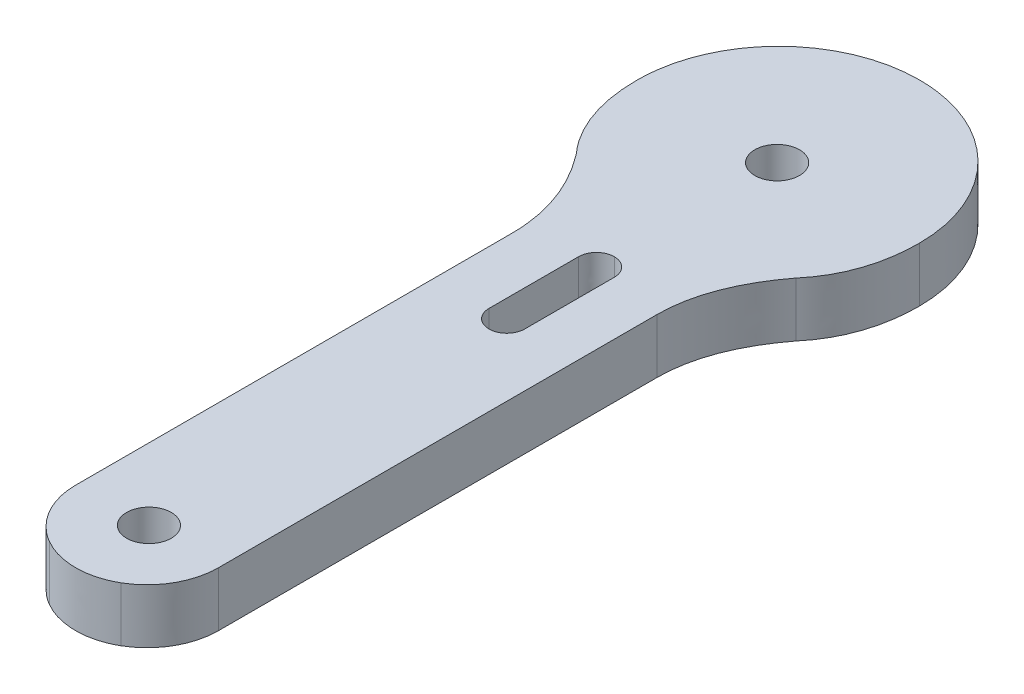
SolidWorks part; units mm, degrees
material "Acrylic (Medium-high impact)"
ref_plane "Front Plane" through (0, 0, 0) normal (0, 0, 1) x (1, 0, 0)
ref_plane "Top Plane" through (0, 0, 0) normal (0, 1, 0) x (1, 0, 0)
ref_plane "Right Plane" through (0, 0, 0) normal (1, 0, 0) x (0, 0, -1)
sketch "Sketch1" plane through (0, 0, 0) normal (0, 1, 0) x (1, 0, 0)
  line L0 (-9.7573, 16.2888) -> (-9.7571, 13.6387) construction
  line L1 (-5.7645, 4.2659) -> (-5.7642, -20.2368)
  line L2 (-13.75, -20.2368) -> (-13.75, 4.1172)
  line L3 (-10.7553, 4.8633) -> (-10.7553, -0.1369)
  line L4 (-8.7589, -0.1369) -> (-8.7589, 4.8633)
  line L5 (-11.0795, -20.1369) -> (-8.4347, -20.1369) construction
  circle A0 centre (-9.7571, -20.1369) radius 1.25
  circle A1 centre (-9.7572, 14.9638) radius 1.25
  spline S2 degree 3 poles (-3.649, 9.9055) (-5.1938, 7.8835) (-5.7645, 5.9594) (-5.7645, 4.2659) knots 1 1 1 1 2 2 2 2
  spline S3 degree 3 poles (-5.7642, -20.2368) (-5.7642, -21.666) (-6.5251, -22.9866) (-7.7606, -23.7011) knots 3 3 3 3 4 4 4 4
  spline S4 degree 3 poles (-7.7606, -23.7011) (-8.9959, -24.4157) (-10.5181, -24.4157) (-11.7535, -23.7011) knots 4 4 4 4 5 5 5 5
  spline S5 degree 3 poles (-11.7535, -23.7011) (-12.989, -22.9866) (-13.75, -21.666) (-13.75, -20.2368) knots 5 5 5 5 6 6 6 6
  spline S6 degree 3 poles (-13.75, 4.1172) (-13.75, 5.8109) (-14.2346, 7.7394) (-15.7794, 9.7615) knots 7 7 7 7 8 8 8 8
  spline S7 degree 3 poles (-15.7794, 9.7615) (-16.932, 11.0366) (-17.6671, 12.7963) (-17.6671, 15.0404) knots 8 8 8 8 9 9 9 9
  spline S8 degree 3 poles (-17.6671, 15.0404) (-17.6671, 19.4054) (-14.1347, 22.9446) (-9.7772, 22.9442) knots 9 9 9 9 10 10 10 10
  spline S9 degree 3 poles (-9.7772, 22.9442) (-5.4201, 22.9442) (-1.8875, 19.4054) (-1.8877, 15.0401) knots 10 10 10 10 11 11 11 11
  spline S10 degree 3 poles (-1.8877, 15.0401) (-1.8877, 12.8796) (-2.5694, 11.1679) (-3.649, 9.9055) knots 11 11 11 11 11.966367 11.966367 11.966367 11.966367
  spline S11 degree 3 poles (-10.7553, -0.1369) (-10.7553, -0.4941) (-10.5649, -0.8244) (-10.256, -1.0031) knots 1 1 1 1 2 2 2 2
  spline S12 degree 3 poles (-10.256, -1.0031) (-9.9474, -1.1816) (-9.5668, -1.1816) (-9.258, -1.0031) knots 2 2 2 2 3 3 3 3
  spline S13 degree 3 poles (-9.258, -1.0031) (-8.9492, -0.8244) (-8.7589, -0.4941) (-8.7589, -0.1369) knots 3 3 3 3 4 4 4 4
  spline S14 degree 3 poles (-8.7589, 4.8633) (-8.7589, 5.4155) (-9.2058, 5.8633) (-9.7571, 5.8633) knots 5 5 5 5 6 6 6 6
  spline S15 degree 3 poles (-9.7571, 5.8633) (-10.3084, 5.8633) (-10.7553, 5.4155) (-10.7553, 4.8633) knots 6 6 6 6 7 7 7 7
  dimension "D1" = 2.5
extrude "Boss-Extrude1" add sketch "Sketch1" along normal blind 3.048
